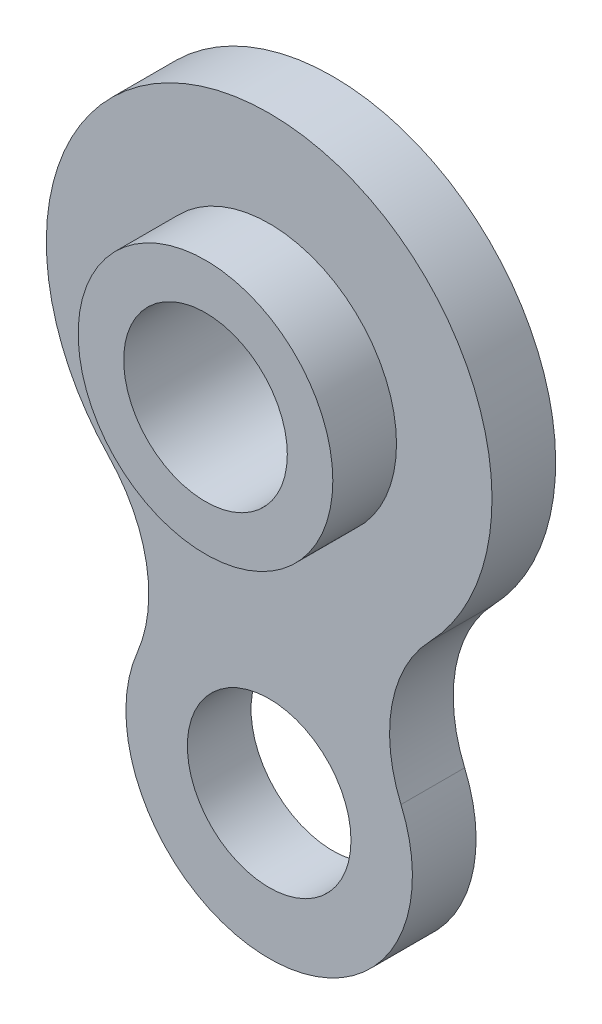
SolidWorks part; units mm, degrees
material "ABS"
ref_plane "Front Plane" through (0, 0, 0) normal (0, 0, 1) x (1, 0, 0)
ref_plane "Top Plane" through (0, 0, 0) normal (0, 1, 0) x (1, 0, 0)
ref_plane "Right Plane" through (0, 0, 0) normal (1, 0, 0) x (0, 0, -1)
sketch "Sketch1" plane through (0, 0, 0) normal (0, 0, 1) x (1, 0, 0)
  line L2 (0, 5.5562) -> (0, -5.5562) construction
  line L6 (0, 5.5562) -> (0, -12.7) construction
  line L9 (17.4625, 13.4938) -> (11.1125, 13.4938)
  line L10 (11.1125, 13.4938) -> (11.1125, 5.5563)
  line L11 (17.4625, 13.4938) -> (17.4625, -5.5562)
  line L12 (17.4625, -5.5562) -> (0, -5.5562)
  line L13 (11.1125, 5.5563) -> (11.1125, -5.5563) construction
  line L14 (14.2875, 13.4938) -> (14.2875, -5.5563) construction
  line L15 (14.2875, 7.9058) -> (14.2875, 0.0318)
  line L16 (0, 5.5562) -> (11.1125, 5.5563)
  line L17 (15.875, -5.5563) -> (15.875, -5.1309)
  line L18 (12.7, -5.5563) -> (15.875, -5.5563)
  line L19 (12.7, -5.5563) -> (12.7, -6.3691)
  line L20 (12.7, -6.3691) -> (15.875, -6.3691)
  line L21 (15.875, -5.5563) -> (15.875, -6.3691)
  circle A0 centre (0, 0) radius 5.5562 construction
  arc A2 (0, 5.5562) -> (0, -5.5562) centre (0, 0) ccw
  circle A4 centre (0, 0) radius 1.7859
  circle A16 centre (14.2875, 7.9058) radius 1.5875
  circle A20 centre (14.2875, 0.0318) radius 1.5875
  circle A22 centre (0, 0) radius 12.7 construction
  circle A25 centre (0, 0) radius 9.1281 construction
  circle A29 centre (14.2875, 10.3188) radius 3.175
  circle A30 centre (14.2875, -2.3813) radius 3.175
  circle A32 centre (0, -9.1281) radius 3.5719
  circle A33 centre (0, -9.1281) radius 1.7859
  circle A34 centre (-6.5741, -6.3327) radius 3.5719
  circle A35 centre (7.1437, -9.1281) radius 3.5719
  point P17 (14.2875, -5.5563)
  point P20 (14.2875, 3.9688)
  dimension "D1" = 7.874
  dimension "D2" = 11.1125
  dimension "D3" = 3.5719
  dimension "D5" = 6.35
  dimension "D6" = 7.1437
  dimension "D8" = 3.175
  dimension "D9" = 0.8128
  dimension "D11" = 3.5719
  dimension "D4" = 19.05
  dimension "D10" = 3.175
sketch "Sketch2" plane through (0, 0, 0) normal (0, 0, 1) x (1, 0, 0)
  circle A0 centre (0, 0) radius 5.5562
  circle A1 centre (0, -9.1281) radius 3.5719
  circle A2 centre (-6.5741, -6.3327) radius 3.5719
  circle A5 centre (0, 0) radius 2.0399
  circle A6 centre (0, -9.1281) radius 2.0399
  circle A7 centre (0, 0) radius 9.1281 construction
  circle A13 centre (6.5741, -6.3327) radius 3.5719
  arc A18 (0, 5.5562) -> (0, -5.5562) centre (0, 0) ccw construction
  circle A19 centre (0, 0) radius 3.175
  dimension "D1" = 4.0799
  dimension "D2" = 4.0799
  dimension "D3" = 6.35
extrude "Boss-Extrude1" add sketch "Sketch2" along normal blind 1.5875 contours A1 A6 | A2 A1 A0 | A13 A0 A1 | A0 A19 region at (5.0072, -2.0194, 0) region at (-2.4105, -5.669, 0) region at (2.4105, -5.669, 0) region at (1.9148, -6.2332, 0)
extrude "Boss-Extrude2" add sketch "Sketch2<6>" along normal blind 3.175 contours A19 A5 region at (-3.0852, 0, 0)
sketch "Sketch2<6>" plane through (0, 0, 0) normal (0, 0, 1) x (1, 0, 0) same geometry as "Sketch2"
